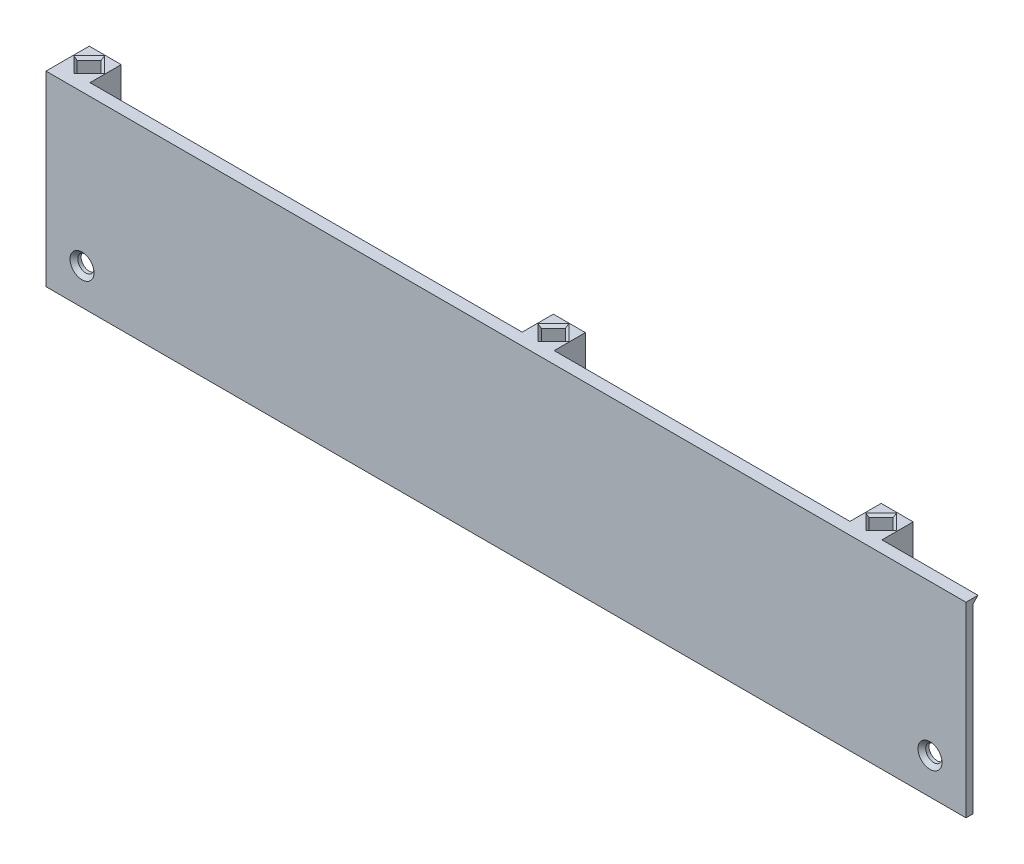
SolidWorks part; units mm, degrees
ref_plane "Front Plane" through (0, 0, 0) normal (0, 0, 1) x (1, 0, 0)
ref_plane "Top Plane" through (0, 0, 0) normal (0, 1, 0) x (1, 0, 0)
ref_plane "Right Plane" through (0, 0, 0) normal (1, 0, 0) x (0, 0, -1)
sketch "Sketch1" plane through (0, 0, 0) normal (0, 0, 1) x (1, 0, 0)
  line L1 (0, 0) -> (243.332, 0)
  line L2 (0, 0) -> (0, 49.395)
  line L3 (0, 49.395) -> (243.332, 49.395)
  line L4 (243.332, 0) -> (243.332, 49.395)
  dimension "D1" = 49.395
  dimension "D2" = 243.332
extrude "Boss-Extrude1" add sketch "Sketch1" along normal blind 1.905
sketch "Sketch2" plane through (0, 0, 0) normal (0, 0, 1) x (1, 0, 0)
  line L0 (243.332, 49.395) -> (0, 49.395) construction
  line L1 (0, 49.395) -> (8.4667, 49.395)
  line L2 (0, 49.395) -> (0, 40.9283)
  line L3 (0, 40.9283) -> (8.4667, 40.9283)
  line L4 (8.4667, 49.395) -> (8.4667, 40.9283)
  line L5 (122.7667, 49.395) -> (131.2333, 49.395)
  line L6 (122.7667, 49.395) -> (122.7667, 40.9283)
  line L7 (122.7667, 40.9283) -> (131.2333, 40.9283)
  line L8 (131.2333, 49.395) -> (131.2333, 40.9283)
  line L9 (243.332, 0) -> (243.332, 49.395) construction
  line L10 (209.4653, 49.395) -> (217.932, 49.395)
  line L11 (209.4653, 49.395) -> (209.4653, 40.9283)
  line L12 (209.4653, 40.9283) -> (217.932, 40.9283)
  line L13 (217.932, 49.395) -> (217.932, 40.9283)
  dimension "D1" = 25.4
  dimension "D2" = 114.3
  dimension "D4" = 8.4667
extrude "Boss-Extrude2" add sketch "Sketch2" against normal blind 9.525
sketch "Sketch3" plane through (0, 49.395, 0) normal (0, 1, 0) x (1, 0, 0)
  line L0 (1.0583, 5.2917) -> (4.2333, 8.4667)
  line L1 (1.0583, 5.2917) -> (4.2333, 2.1167)
  line L2 (4.2333, 8.4667) -> (7.4083, 5.2917)
  line L3 (4.2333, 2.1167) -> (7.4083, 5.2917)
  line L4 (1.0583, 5.2917) -> (7.4083, 5.2917) construction
  line L5 (4.2333, 8.4667) -> (4.2333, 2.1167) construction
  line L6 (123.825, 5.2917) -> (127, 8.4667)
  line L7 (123.825, 5.2917) -> (127, 2.1167)
  line L8 (127, 8.4667) -> (130.175, 5.2917)
  line L9 (127, 2.1167) -> (130.175, 5.2917)
  line L10 (123.825, 5.2917) -> (130.175, 5.2917) construction
  line L11 (127, 8.4667) -> (127, 2.1167) construction
  line L12 (210.5237, 5.2917) -> (213.6987, 8.4667)
  line L13 (210.5237, 5.2917) -> (213.6987, 2.1167)
  line L14 (213.6987, 8.4667) -> (216.8737, 5.2917)
  line L15 (213.6987, 2.1167) -> (216.8737, 5.2917)
  line L16 (210.5237, 5.2917) -> (216.8737, 5.2917) construction
  line L17 (213.6987, 8.4667) -> (213.6987, 2.1167) construction
  line L18 (8.4667, 9.525) -> (0, 9.525) construction
  line L19 (131.2333, 9.525) -> (122.7667, 9.525) construction
  line L20 (217.932, 9.525) -> (209.4653, 9.525) construction
  line L21 (8.4667, 9.525) -> (0, 9.525) construction
  point P1 (4.2333, 5.2917)
  point P2 (127, 5.2917)
  point P3 (213.6987, 5.2917)
  point P13 (4.2333, 9.525)
  point P20 (127, 9.525)
  point P23 (213.6987, 9.525)
  dimension "D1" = 6.35
  dimension "D2" = 4.2333
extrude "Cut-Extrude1" cut sketch "Sketch3" against normal blind 6.35
chamfer "Chamfer1" distance 0.635 angle 45 24 edges at (212.1112, 43.045, -6.8792) (215.2862, 43.045, -6.8792) (215.2862, 43.045, -3.7042) (212.1112, 43.045, -3.7042) (2.6458, 43.045, -6.8792) (5.8208, 43.045, -6.8792) (5.8208, 43.045, -3.7042) (2.6458, 43.045, -3.7042) (125.4125, 43.045, -6.8792) (128.5875, 43.045, -6.8792) (128.5875, 43.045, -3.7042) (125.4125, 43.045, -3.7042) (212.1112, 49.395, -6.8792) (212.1112, 49.395, -3.7042) (215.2862, 49.395, -6.8792) (215.2862, 49.395, -3.7042) (2.6458, 49.395, -6.8792) (2.6458, 49.395, -3.7042) (5.8208, 49.395, -6.8792) (5.8208, 49.395, -3.7042) (128.5875, 49.395, -3.7042) (128.5875, 49.395, -6.8792) (125.4125, 49.395, -6.8792) (125.4125, 49.395, -3.7042)
sketch "Sketch4" plane through (243.332, 0, 0) normal (1, 0, 0) x (0, 0, -1)
  line L0 (0, 49.395) -> (1.27, 49.395)
  line L1 (9.525, 49.395) -> (0, 49.395) construction
  line L2 (1.27, 49.395) -> (0, 48.125)
  line L3 (0, 0) -> (0, 49.395) construction
  line L4 (0, 48.125) -> (0, 49.395)
  dimension "D1" = 1.27
extrude "Boss-Extrude3" add sketch "Sketch4" against normal up to surface (243.332 mm away) up to face at (0, 30.1078, -2.54)
sketch "Sketch5" plane through (0, 0, 1.905) normal (0, 0, 1) x (1, 0, 0)
  line L0 (0, 9.525) -> (9.525, 9.525) construction
  line L1 (9.525, 9.525) -> (9.525, 0) construction
  line L2 (0, 0) -> (243.332, 0) construction
  line L3 (243.332, 9.525) -> (233.807, 9.525) construction
  line L4 (243.332, 0) -> (243.332, 49.395) construction
  line L5 (233.807, 9.525) -> (233.807, 0) construction
  line L6 (0, 49.395) -> (0, 0) construction
  point P11 (233.807, 9.525)
  point P15 (9.525, 9.525)
  dimension "D1" = 9.525
hole_wizard "#6 Clearance Hole1" positions "Sketch5" profile "Sketch6" hole size "#6" standard "ANSI Inch" end condition through all
sketch "Sketch6" plane through (9.525, 9.525, 1.905) normal (1, 0, 0) x (0, -1, 0)
  line L0 (0, 0) -> (0, 11.43)
  line L1 (0, 11.43) -> (2.1526, 11.43)
  line L2 (2.1526, 11.43) -> (2.1526, 1.0224)
  line L3 (2.1526, 1.0224) -> (3.175, 0)
  line L5 (3.175, 0) -> (0, 0)
  line L6 (-2.1526, 1.0224) -> (-3.175, 0) construction
  line L11 (0, -6.35) -> (0, 107.95) construction
  dimension "Thru Hole Dia." = 4.3053
  dimension "Thru Hole Depth" = 11.43
  dimension "Near C'Sink Dia." = 6.35
  dimension "Near C'Sink Angle" = 90
